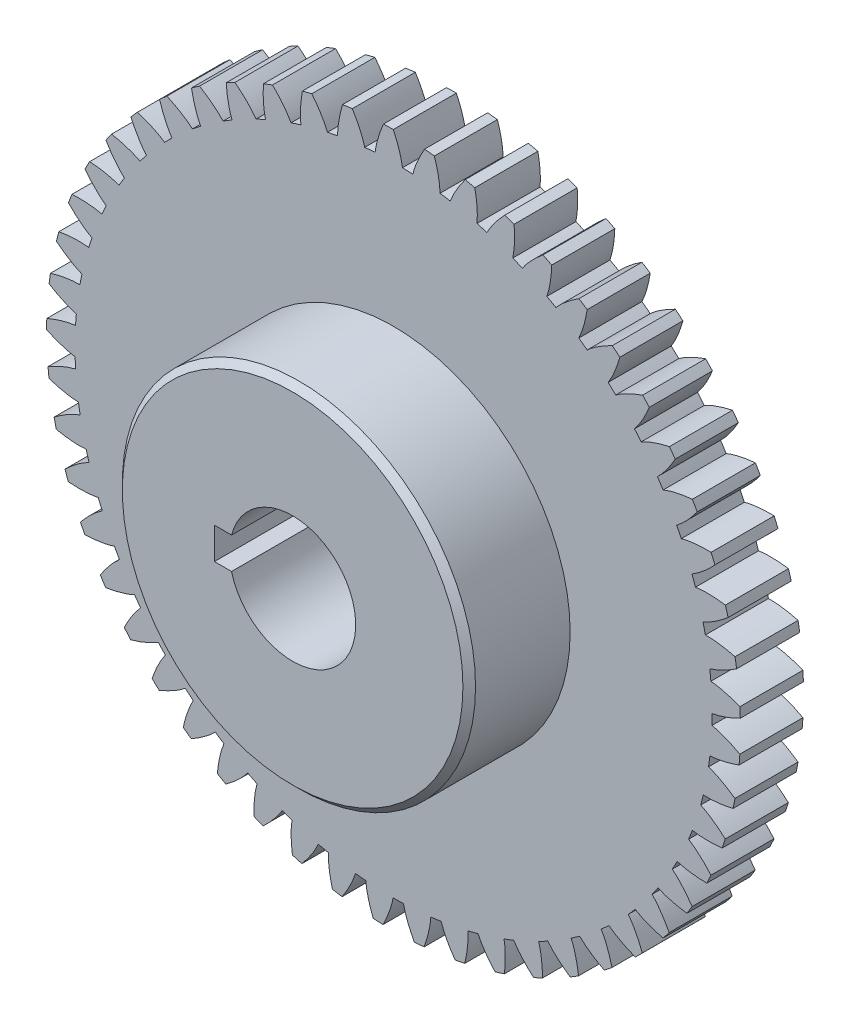
SolidWorks part; units mm, degrees
ref_plane "前视基准面" through (0, 0, 0) normal (0, 0, 1) x (1, 0, 0)
ref_plane "上视基准面" through (0, 0, 0) normal (0, 1, 0) x (1, 0, 0)
ref_plane "右视基准面" through (0, 0, 0) normal (1, 0, 0) x (0, 0, -1)
sketch "草图1" plane through (0, 0, 0) normal (0, 0, 1) x (1, 0, 0)
  circle A0 centre (0, 0) radius 25.25
extrude "凸台-拉伸1" add sketch "草图1" along normal blind 5
sketch "草图2" plane through (0, 0, 0) normal (0, 0, 1) x (1, 0, 0)
  arc A0 (27.4526, 1.6134) -> (27.4873, 0.8353) centre (0, 0) cw
  arc A1 (24.8031, 2.2154) -> (24.9019, 0) centre (0, 0) cw
  spline S0 degree 3 poles (27.4873, 0.8353) (27.2074, 0.6937) (26.7823, 0.4994) (26.2031, 0.2844) (25.6321, 0.1085) (25.1958, 0.0175) (24.9019, 0) knots 0 0 0 0 0.344416 0.512486 0.677795 1 1 1 1
  spline S1 degree 3 poles (27.4526, 1.6134) (27.1612, 1.7296) (26.7205, 1.8853) (26.1245, 2.0479) (25.5401, 2.1724) (25.0975, 2.2242) (24.8031, 2.2154) knots 0 0 0 0 0.344416 0.512486 0.677795 1 1 1 1
extrude "凸台-拉伸2" add sketch "草图2" along normal blind 5
pattern_circular "阵列(圆周)1" count 53 over 360 about axis through (0, 0, 5) along (0, 0, -1) of "凸台-拉伸2"
sketch "草图3" plane through (0, 0, 5) normal (0, 0, 1) x (1, 0, 0)
  circle A0 centre (0, 0) radius 14
  dimension "D1" = 28
extrude "凸台-拉伸3" add sketch "草图3" along normal blind 8
chamfer "倒角1" distance 0.5 angle 45 1 edges at (14, 0, 13)
sketch "草图4" plane through (0, 0, 13) normal (0, 0, 1) x (1, 0, 0)
  line L1 (-6.2, 1.25) -> (-3.8, 1.25)
  line L2 (-6.2, 1.25) -> (-6.2, -1.25)
  line L3 (-6.2, -1.25) -> (-3.8, -1.25)
  line L4 (-3.8, 1.25) -> (-3.8, -1.25)
  line L5 (-6.2, 1.25) -> (-3.8, -1.25) construction
  line L6 (-6.2, -1.25) -> (-3.8, 1.25) construction
  circle A0 centre (0, 0) radius 5
  point P3 (-5, 0)
  dimension "D1" = 10
  dimension "D2" = 11.2
  dimension "D3" = 2.5
extrude "切除-拉伸1" cut sketch "草图4" against normal through all contours L3 A0 L1 L4 | A0 L1 L2 L3 | L1 A0 L3 L4 region at (-5.5728, 0, 13) region at (0.1658, 0, 13) region at (-4.3747, 0, 13)
